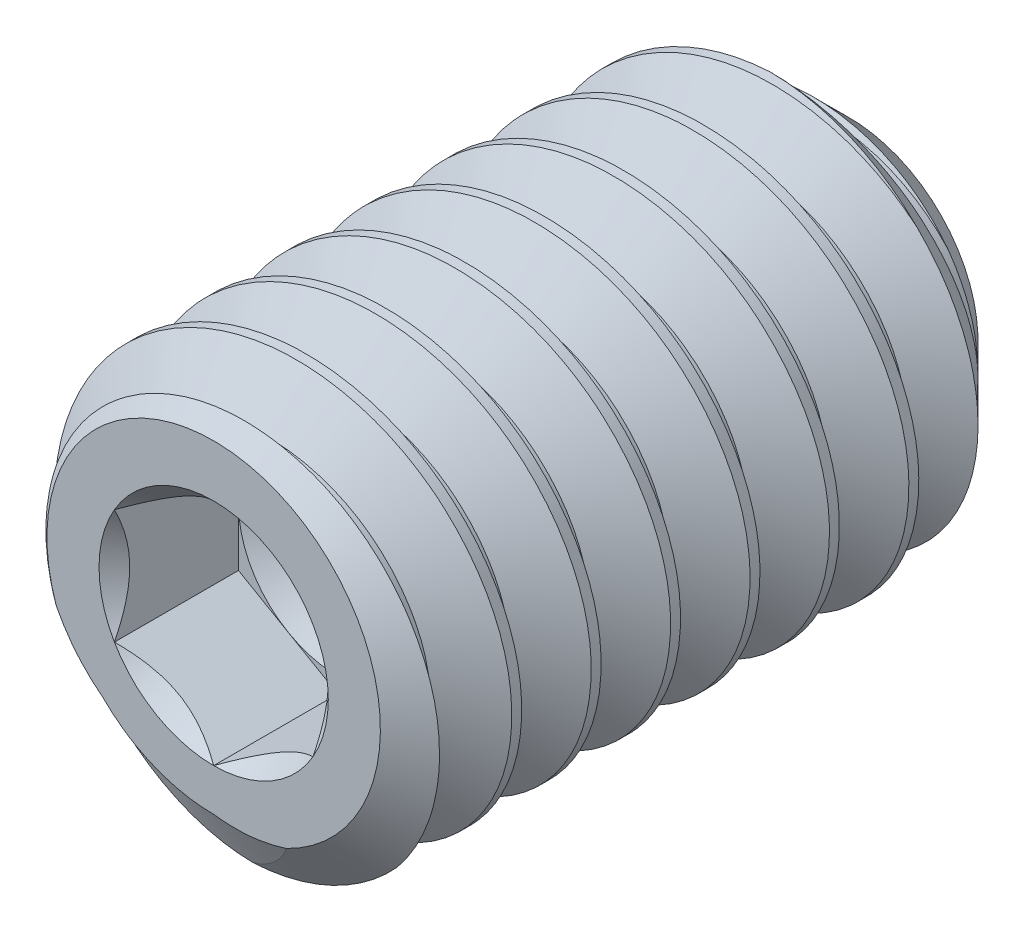
SolidWorks part; units mm, degrees
ref_plane "Front" through (0, 0, 0) normal (0, 0, 1) x (1, 0, 0)
ref_plane "Top" through (0, 0, 0) normal (0, 1, 0) x (1, 0, 0)
ref_plane "Right" through (0, 0, 0) normal (1, 0, 0) x (0, 0, -1)
sketch "Sketch22" plane through (0, 0, 0) normal (1, 0, 0) x (0, 0, -1)
  line L0 (-3.175, 0) -> (-3.175, 1.6662)
  line L1 (-3.175, 1.6662) -> (-2.8833, 2.0828)
  line L2 (-2.8833, 2.0828) -> (2.3813, 2.0828)
  line L3 (2.3813, 2.0828) -> (3.175, 1.2891)
  line L4 (-0.251, 2.0828) -> (-0.251, -2.0828) construction
  line L5 (3.175, 0) -> (-3.175, 0)
  line L7 (3.175, 0) -> (3.175, 1.2891)
  line L10 (-3.175, 1.6662) -> (-3.175, -1.6662) construction
  point P13 (-0.251, 0)
  dimension "Length" = 6.35
  dimension "D3" = 35
  dimension "D1" = 3.3325
  dimension "Dia" = 4.1656
  dimension "D2" = 0.7937
  dimension "D4" = 45
revolve "Revolve1" add sketch "Sketch22" angle 360 about L5
ref_plane "Plane1" through (0, 0, -3.175) normal (0, 0, 1) x (1, 0, 0)
sketch "Sketch27" plane through (0, 0, -3.175) normal (0, 0, 1) x (1, 0, 0)
  circle A0 centre (0, 0) radius 2.0828 construction
  circle A1 centre (0, 0) radius 2.0828
curve "Helix/Spiral1" pitch 0.7937 height 7.1437 radius 2.0828 centre (0, 0, -3.175) axis (0, 0, 1) start towards (1, 0, 0)
sketch "Sketch28" plane through (0, 0, 0) normal (1, 0, 0) x (0, 0, -1)
  line L0 (3.175, 2.0828) -> (3.8695, 2.0828)
  line L1 (3.8695, 2.0828) -> (3.5719, 1.5672)
  line L2 (3.5719, 1.5672) -> (3.4727, 1.5672)
  line L3 (3.4727, 1.5672) -> (3.175, 2.0828)
  line L4 (3.3238, 1.825) -> (3.7207, 1.825) construction
  line L6 (-2.8833, 2.0828) -> (2.3813, 2.0828) construction
  line L7 (3.175, 2.2911) -> (3.175, -2.2911) construction
  dimension "D1" = 0.0992
  dimension "D3" = 60
  dimension "D2" = 0.3969
sweep "Cut-Sweep2" cut profiles "Sketch28" path "Helix/Spiral1" align with end faces yes
sketch "Sketch23" plane through (0, 0, 3.175) normal (0, 0, 1) x (1, 0, 0)
  line L1 (0, 1.1457) -> (-0.9922, 0.5728)
  line L2 (-0.9922, 0.5728) -> (-0.9922, -0.5728)
  line L3 (-0.9922, -0.5728) -> (0, -1.1457)
  line L4 (0, -1.1457) -> (0.9922, -0.5728)
  line L5 (0.9922, -0.5728) -> (0.9922, 0.5728)
  line L6 (0.9922, 0.5728) -> (0, 1.1457)
  circle A0 centre (0, 0) radius 0.9922 construction
  dimension "Hex" = 1.9844
extrude "Cut-Extrude10" cut sketch "Sketch23" against normal blind 1.2402
sketch "Sketch24" plane through (0, 0, 3.175) normal (0, 0, 1) x (1, 0, 0)
  circle A0 centre (0, 0) radius 1.1457
extrude "Cut-Extrude11" cut sketch "Sketch24" against normal through all draft 45
sketch "Sketch26" plane through (0, 0, 1.9348) normal (0, 0, 1) x (1, 0, 0)
  circle A0 centre (0, 0) radius 0.9922 construction
  circle A1 centre (0, 0) radius 0.9922
extrude "Cut-Extrude12" cut sketch "Sketch26" against normal through all draft 60
sketch "Sketch30" plane through (0, 0, 0) normal (1, 0, 0) x (0, 0, -1)
  line L0 (-2.8833, 2.0828) -> (2.3813, 2.0828) construction
  line L1 (-3.175, 0) -> (-3.175, 1.6662) construction
  line L2 (3.175, 0) -> (3.175, 1.2891) construction
  point P0 (-3.175, 2.0828)
  point P1 (3.175, 2.0828)
  point P2 (3.175, -2.0828)
  point P11 (1.1906, -2.0828)
  dimension "D1" = 1.9844
equation "\"D1@Sketch28\" = \"D4@Helix/Spiral1\" * .125"
equation "\"D3@Helix/Spiral1\" = \"Length@Sketch22\" + \"D4@Helix/Spiral1\""
equation "\"D1@Sketch30\" = \"D4@Helix/Spiral1\" * 2.5"
equation "\"hex Depth@Cut-Extrude10\" = \"Hex@Sketch23\" * .625"
equation "\"D2@Sketch28\" = \"D4@Helix/Spiral1\" * .5"
equation "\"D1@Sketch22\" = \"Dia@Sketch22\" * .8"
equation "\"D2@Sketch22\" = \"D4@Helix/Spiral1\""
